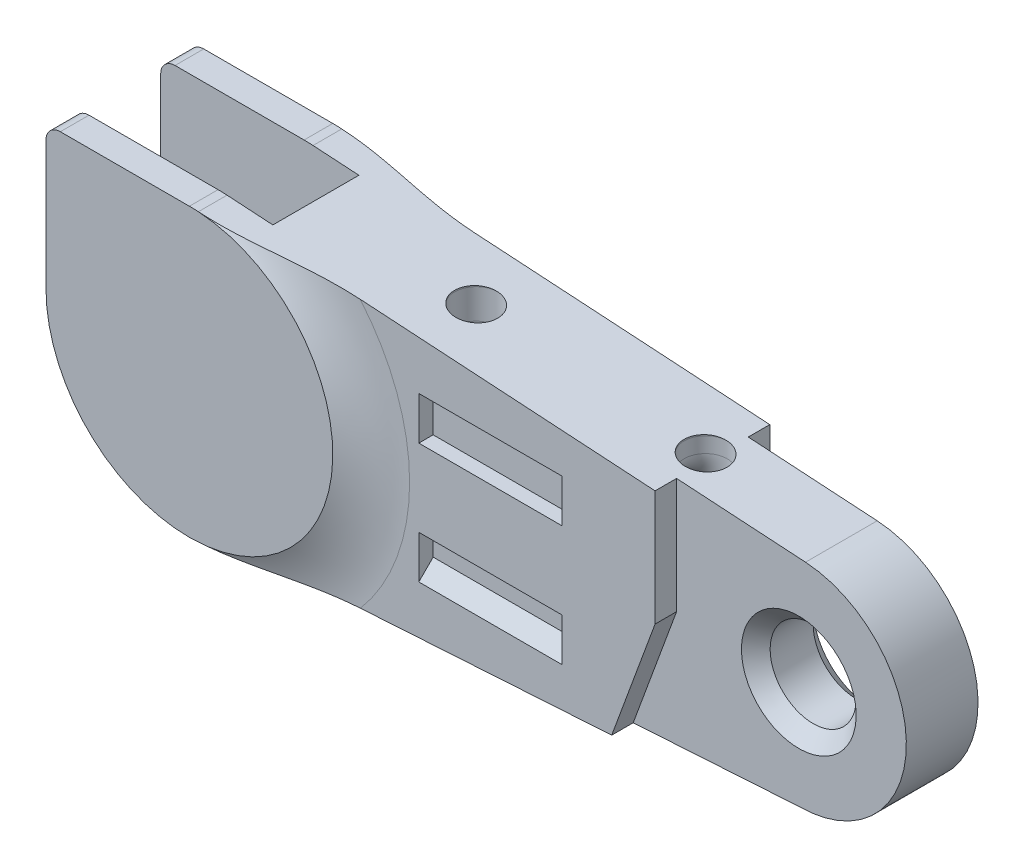
SolidWorks part; units mm, degrees
ref_plane "Front Plane" through (0, 0, 0) normal (0, 0, 1) x (1, 0, 0)
ref_plane "Top Plane" through (0, 0, 0) normal (0, 1, 0) x (1, 0, 0)
ref_plane "Right Plane" through (0, 0, 0) normal (1, 0, 0) x (0, 0, -1)
sketch "Sketch1" plane through (0, 0, 0) normal (0, 0, 1) x (1, 0, 0)
  line L0 (55, 0) -> (-55, 0) construction
  line L1 (0, -55) -> (0, 55) construction
  line L2 (-19.375, 9.9804) -> (20.4688, 7.4853)
  line L3 (-20, -10) -> (20, -7.5)
  line L4 (-20, 10) -> (-29, 10)
  line L5 (-30, 9) -> (-30, 0)
  arc A0 (-30, 0) -> (-20, 10) centre (-20, 0) ccw
  circle A1 centre (20, 0) radius 7.5
  circle A2 centre (-20, 0) radius 2.5
  circle A3 centre (20, 0) radius 3
  arc A4 (-29, 10) -> (-30, 9) centre (-29, 9) ccw
  dimension "D1" = 20
  dimension "D2" = 15
  dimension "D5" = 5
  dimension "D6" = 6
  dimension "D7" = 1
  dimension "D3" = 40
  dimension "D4" = 20
extrude "Boss-Extrude1" add sketch "Sketch1" along normal mid plane 8 contours A1 L2 A0 L3 region at (0.7062, 0.0129, 0)
extrude "Boss-Extrude2" add sketch "Sketch1<3>" along normal mid plane 10 contours A0 L3 A2 region at (-10.2876, 0.3026, 0)
sketch "Sketch1<3>" plane through (0, 0, 0) normal (0, 0, 1) x (1, 0, 0) same geometry as "Sketch1"
extrude "Boss-Extrude3" add sketch "Sketch1<5>" along normal mid plane 9 contours A1 A3 region at (25.3119, 4.9897, 0)
sketch "Sketch1<5>" plane through (0, 0, 0) normal (0, 0, 1) x (1, 0, 0) same geometry as "Sketch1"
fillet "Fillet1" radius 10 2 edges at (-10.0049, 0.3114, -4) (-10.0049, 0.3114, 4)
extrude "Cut-Extrude2" cut sketch "Sketch1<6>" against normal mid plane 6 contours A0 L3 A2 region at (-10.2876, 0.3026, 0)
sketch "Sketch1<6>" plane through (0, 0, 0) normal (0, 0, 1) x (1, 0, 0) same geometry as "Sketch1"
sketch "Sketch2" plane through (0, 0, 0) normal (0, 0, 1) x (1, 0, 0)
  line L0 (-9.5, 0) -> (-9.5, -10.5)
  line L1 (-9.5, -10.5) -> (-20, -10.5)
  line L2 (11.4759, 0) -> (8, -9.4488)
  line L3 (8, -9.4488) -> (20, -9.4488)
  line L4 (20, -9.4488) -> (20, -8)
  line L5 (11.4759, 0) -> (16.0501, 0)
  line L6 (55, 0) -> (-55, 0) construction
  line L7 (11.4759, 0) -> (11.4759, 8.8777)
  line L8 (11.4759, 8.8777) -> (20, 8)
  arc A0 (-9.5, 0) -> (-20, -10.5) centre (-20, 0) ccw
  arc A1 (20, -8) -> (20, 8) centre (20, 0) ccw
  dimension "D1" = 21
  dimension "D2" = 16
  dimension "D3" = 12
extrude "Cut-Extrude3" cut sketch "Sketch2" against normal mid plane 6 contours L0 A0 L1 region at (-19.4786, -0.5214, 0)
extrude "Cut-Extrude4" cut sketch "Sketch2<3>" along normal blind 7.5 from offset 10 contours A1 region at (18.245, -0.6687, 0) offset against normal yes
sketch "Sketch2<3>" plane through (0, 0, 0) normal (0, 0, 1) x (1, 0, 0) same geometry as "Sketch2"
mirror "Mirror1" about plane through (0, 0, 0) normal (0, 0, 1) of "Cut-Extrude4"
sketch "Sketch3" plane through (0, 0, 0) normal (0, 0, 1) x (1, 0, 0)
  line L0 (-5, 9.0803) -> (-5, 7)
  line L1 (-9.0909, 9.3364) -> (-19.375, 9.9804) construction
  line L2 (-2, 4) -> (8, 4)
  line L3 (11, 7) -> (11, 8.0783)
  line L4 (-9.0909, 9.3364) -> (11.4759, 8.0485) construction
  line L5 (-5, 9.0803) -> (-5, 11.3767)
  line L7 (11, 8.0783) -> (11, 10.9782)
  line L8 (0, -55) -> (0, 55) construction
  line L9 (55, 0) -> (-55, 0) construction
  arc A2 (11, 7) -> (8, 4) centre (8, 7) cw
  arc A3 (-2, 4) -> (-5, 7) centre (-2, 7) cw
  point P24 (11, 4)
  point P27 (-5, 4)
  dimension "D1" = 16
  dimension "D2" = 5
  dimension "D3" = 4
sweep "Cut-Sweep5" cut path "Sketch3" circular profile diameter 3 parameters "D3"=3
mirror "Mirror2" about plane through (0, 0, 0) normal (0, 1, 0) of "Cut-Sweep5"
extrude "Boss-Extrude4" add sketch "Sketch1<7>" along normal mid plane 10 contours A2 region at (-20, 0, 0)
sketch "Sketch1<7>" plane through (0, 0, 0) normal (0, 0, 1) x (1, 0, 0) same geometry as "Sketch1"
chamfer "Chamfer1" distance 1 angle 45 4 edges at (23, 0, -2.5) (17, 0, 2.5) (-17.5, 0, 3) (-17.5, 0, -3)
sketch "Sketch139" plane through (0, 0, 0) normal (1, 0, 0) x (0, 0, -1)
  line L0 (4, 8.6925) -> (4, 5.6925)
  line L1 (4, 9.3364) -> (4, 8.0485) construction
  line L2 (4, 8.0485) -> (4, 0) construction
  line L3 (4, 5.6925) -> (3, 4.6925)
  line L4 (3, 4.6925) -> (3, 2.6925)
  line L5 (3, 2.6925) -> (5.5203, 2.6925)
  line L6 (5.5203, 2.6925) -> (5.5203, 8.6925)
  line L7 (5.5203, 8.6925) -> (4, 8.6925)
  dimension "D1" = 3
  dimension "D2" = 1
  dimension "D3" = 1
  dimension "D4" = 2
extrude "Cut-Extrude5" cut sketch "Sketch139" against normal mid plane 10
mirror "Mirror3" about plane through (0, 0, 0) normal (0, 1, 0) of "Cut-Extrude5"
mirror "Mirror4" about plane through (0, 0, 0) normal (0, 0, 1) of "Mirror3"
